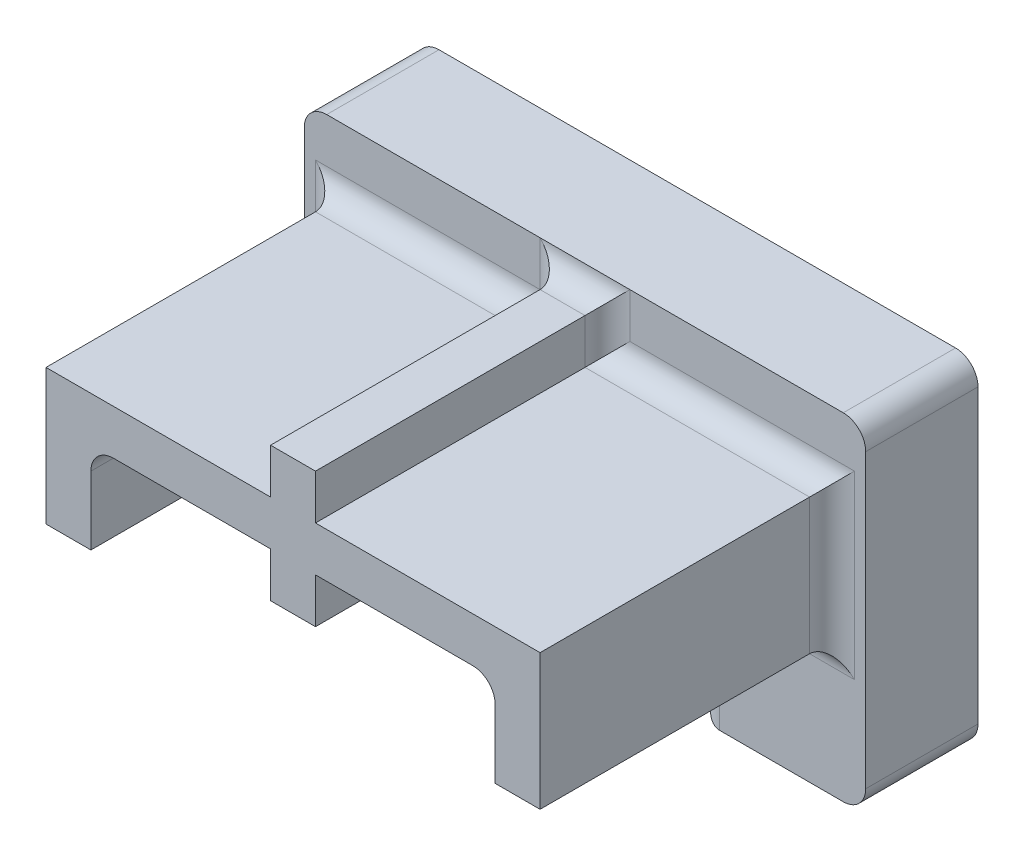
SolidWorks part; units mm, degrees
ref_plane "Plano frontal" through (0, 0, 0) normal (0, 0, 1) x (1, 0, 0)
ref_plane "Plano superior" through (0, 0, 0) normal (0, 1, 0) x (1, 0, 0)
ref_plane "Plano direito" through (0, 0, 0) normal (1, 0, 0) x (0, 0, -1)
sketch "Esboço1" plane through (0, 0, 0) normal (0, 0, 1) x (1, 0, 0)
  line L0 (-2.9579, -18.6872) -> (-2.9579, -8.6872)
  line L1 (-17.9579, 11.3128) -> (32.0421, 11.3128)
  line L2 (-17.9579, 11.3128) -> (-17.9579, -18.6872)
  line L3 (-17.9579, -18.6872) -> (32.0421, -18.6872)
  line L4 (32.0421, 11.3128) -> (32.0421, -18.6872)
  line L5 (-2.9579, -8.6872) -> (17.0421, -8.6872)
  line L6 (17.0421, -18.6872) -> (17.0421, -8.6872)
  line L7 (7.0421, 11.3128) -> (7.0421, -18.6872) construction
  arc A0 (-2.9579, -13.6872) -> (17.0421, -13.6872) centre (7.0421, -21.1872) cw
  point P11 (7.0421, -8.6872)
  point P15 (-2.9579, -13.6872)
  point P16 (17.0421, -13.6872)
  dimension "D1" = 50
  dimension "D2" = 30
  dimension "D3" = 10
  dimension "D4" = 15
extrude "Ressalto-extrusão1" add sketch "Esboço1" along normal blind 10 contours L7 L1 L2 L3 L0 L5 | L0 A0 L5 | L1 L7 L5 L6 L3 L4 | L5 A0 L6 region at (-6.6117, -2.1487, 0) region at (-0.5688, -10.1167, 0) region at (20.696, -2.1487, 0) region at (14.6531, -10.1167, 0)
fillet "Filete1" radius 2 10 edges at (-2.9579, -18.6872, 5) (-2.9579, -16.1872, 10) (-2.9579, -16.1872, 0) (17.0421, -16.1872, 10) (17.0421, -18.6872, 5) (17.0421, -16.1872, 0) (7.0421, -8.6872, 10) (7.0421, -8.6872, 0) (-2.9579, -13.6872, 5) (17.0421, -13.6872, 5)
fillet "Filete2" radius 2 4 edges at (32.0421, 11.3128, 5) (32.0421, -18.6872, 5) (-17.9579, 11.3128, 5) (-17.9579, -18.6872, 5)
sketch "Esboço2" plane through (0, 0, 10) normal (0, 0, 1) x (1, 0, 0)
  line L0 (7.0421, 11.3128) -> (7.0421, -4.6872) construction
  line L1 (-15.9579, 11.3128) -> (30.0421, 11.3128) construction
  line L2 (7.0421, 3.3128) -> (32.0421, 3.3128) construction
  line L3 (32.0421, 9.3128) -> (32.0421, -16.6872) construction
  line L4 (-1.9579, 11.3128) -> (16.0421, 11.3128)
  line L5 (5.0421, 9.3128) -> (5.0421, 5.3128)
  line L7 (5.0421, 5.3128) -> (29.0421, 5.3128)
  line L8 (29.0421, 5.3128) -> (29.0421, 1.3128)
  line L9 (5.0421, 1.3128) -> (25.0421, 1.3128)
  line L10 (25.0421, 1.3128) -> (25.0421, -6.7711)
  line L11 (25.0421, -6.7711) -> (29.0421, -6.7711)
  line L12 (29.0421, -6.7711) -> (29.0421, 1.3128)
  line L13 (9.0421, 1.3128) -> (-10.9579, 1.3128)
  line L14 (-10.9579, 1.3128) -> (-10.9579, -6.7711)
  line L15 (-10.9579, -6.7711) -> (-14.9579, -6.7711)
  line L16 (-14.9579, -6.7711) -> (-14.9579, 1.3128)
  line L17 (-14.9579, 5.3128) -> (-14.9579, 1.3128)
  line L18 (9.0421, 5.3128) -> (-14.9579, 5.3128)
  line L19 (9.0421, 9.3128) -> (9.0421, 5.3128)
  line L20 (9.0421, -2.6872) -> (5.0421, -2.6872)
  line L21 (5.0421, 1.3128) -> (5.0421, -2.6872)
  line L22 (9.0421, 1.3128) -> (9.0421, -2.6872)
  line L23 (9.0421, 9.3128) -> (5.0421, 9.3128)
  point P17 (29.0421, 3.3128)
  dimension "D1" = 4
  dimension "D2" = 20
  dimension "D3" = 4
  dimension "D4" = 4
  dimension "D5" = 4
  dimension "D6" = 6
  dimension "D7" = 4
extrude "Ressalto-extrusão2" add sketch "Esboço2" along normal blind 26 contours L23 L19 L18 L17 L16 L15 L14 L13 L22 L20 L21 L9 L10 L11 L12 L8 L7 L5 | L22 L9 L21 L20 | L19 L23 L5 L7 region at (7.0421, 7.3128, 10) region at (7.0421, 1.6892, 10) region at (7.0421, -0.6872, 10)
fillet "Filete4" radius 2 2 edges at (-10.9579, 1.3128, 23) (25.0421, 1.3128, 23)
fillet "Filete6" radius 2 9 edges at (-4.9579, 5.3128, 10) (19.0421, 5.3128, 10) (29.0421, -0.7292, 10) (-14.9579, -0.7292, 10) (-12.9579, -6.7711, 10) (27.0421, -6.7711, 10) (9.0421, 7.3128, 10) (5.0421, 7.3128, 10) (7.0421, 9.3128, 10)
sketch "Esboço4" plane through (0, 0, 36) normal (0, 0, 1) x (1, 0, 0)
  line L0 (7.0421, 9.3128) -> (7.0421, 2.0628) construction
  line L1 (32.0421, 10.5628) -> (-17.9579, 10.5628)
  line L2 (32.0421, 10.5628) -> (32.0421, -45.4372)
  line L3 (32.0421, -45.4372) -> (-17.9579, -45.4372)
  line L4 (-17.9579, 10.5628) -> (-17.9579, -45.4372)
  line L5 (9.0421, 9.3128) -> (5.0421, 9.3128) construction
  line L7 (7.0421, 10.5628) -> (7.0421, -45.4372) construction
  line L8 (7.0421, -13.6435) -> (7.0421, -45.4372)
  line L11 (-17.9579, -18.6435) -> (32.0421, -18.6435) construction
  circle A0 centre (7.0421, -18.6435) radius 5
  dimension "D1" = 56
  dimension "D2" = 50
  dimension "D3" = 1.25
extrude "Ressalto-extrusão4" [suppressed] add sketch "Esboço4" along normal blind 10
sketch "Esboço5" [suppressed] plane through (0, 0, 46) normal (0, 0, 1) x (1, 0, 0)
  line L0 (7.0421, 10.5628) -> (7.0421, -45.4372) construction
  line L1 (32.0421, 10.5628) -> (-17.9579, 10.5628) construction
  line L2 (32.0421, -45.4372) -> (-17.9579, -45.4372) construction
  line L3 (-13.9579, -40.8372) -> (28.0421, -40.8372)
  line L4 (-13.9579, -40.8372) -> (-13.9579, 2.6628)
  line L5 (-17.9579, 10.5628) -> (-17.9579, -45.4372) construction
  line L6 (-13.9579, 2.6628) -> (28.0421, 2.6628)
  line L7 (32.0421, 6.6628) -> (-17.9579, 6.6628)
  line L8 (-17.9579, 6.6628) -> (-17.9579, -45.4372)
  line L9 (-17.9579, -45.4372) -> (32.0421, -45.4372)
  line L10 (32.0421, 6.6628) -> (32.0421, -45.4372)
  line L11 (28.0421, -40.8372) -> (28.0421, 2.6628)
  point P11 (7.0421, 2.6628)
  point P18 (7.0421, -40.8372)
  point P20 (7.0421, 6.6628)
  dimension "D1" = 43.5
  dimension "D2" = 4
  dimension "D3" = 4.6
  dimension "D4" = 4
extrude "Ressalto-extrusão5" [suppressed] add sketch "Esboço5" along normal blind 25
fillet "Filete7" [suppressed] radius 2
fillet "Filete8" [suppressed] radius 2
